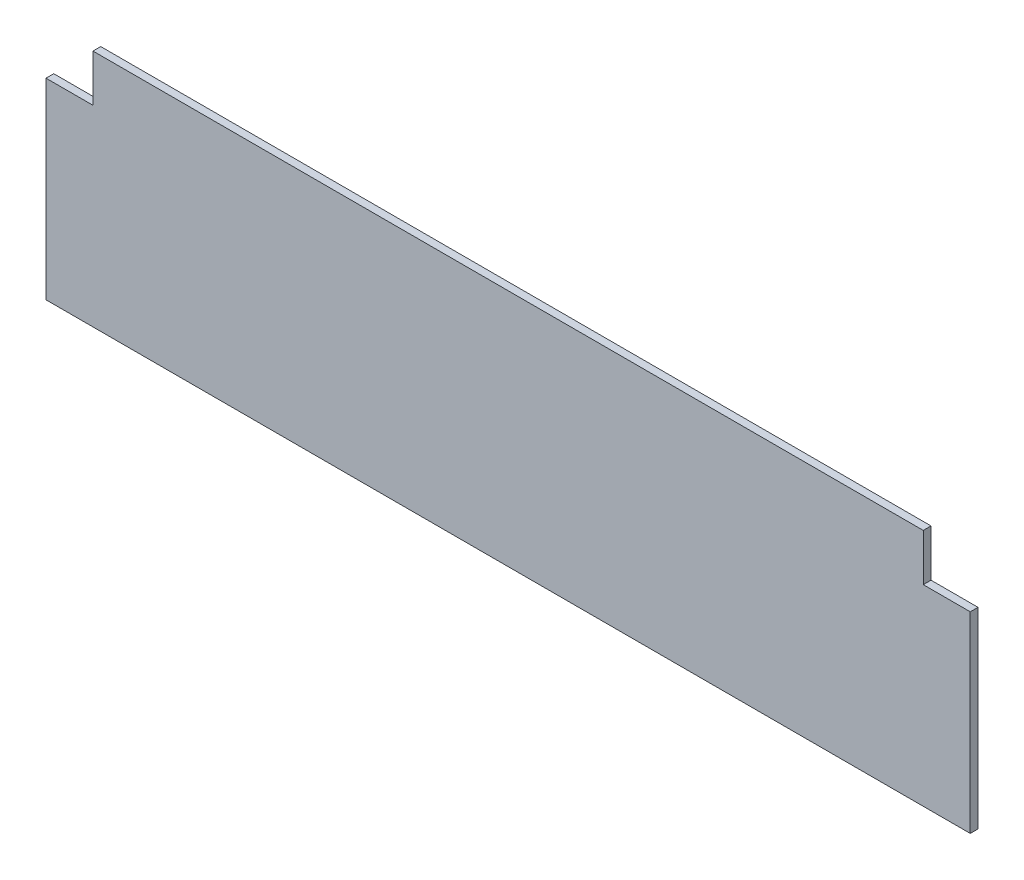
SolidWorks part; units mm, degrees
material "Balsa"
ref_plane "Front Plane" through (0, 0, 0) normal (0, 0, 1) x (1, 0, 0)
ref_plane "Top Plane" through (0, 0, 0) normal (0, 1, 0) x (1, 0, 0)
ref_plane "Right Plane" through (0, 0, 0) normal (1, 0, 0) x (0, 0, -1)
sketch "Sketch1" plane through (0, 0, 0) normal (0, 0, 1) x (1, 0, 0)
  line L0 (393.4, -121.5124) -> (393.4, -39.8043)
  line L1 (393.4, -39.8043) -> (0, -39.8043) construction
  line L2 (0, -39.8043) -> (0, -121.5124)
  line L3 (0, -121.5124) -> (393.4, -121.5124)
  line L4 (0, -138.3774) -> (0, -39.8043) construction
  line L5 (373.4, -39.8043) -> (20, -39.8043) construction
  line L6 (373.4, -39.8043) -> (373.4, -19.8043)
  line L7 (373.4, -19.8043) -> (20, -19.8043)
  line L8 (20, -39.8043) -> (20, -19.8043)
  line L9 (373.4, -39.8043) -> (20, -19.8043) construction
  line L10 (373.4, -19.8043) -> (20, -39.8043) construction
  line L13 (20.7, -19.8043) -> (372.7, -19.8043) construction
  line L14 (393.4, -39.8043) -> (393.4, -138.3812) construction
  line L19 (393.4, -39.8043) -> (373.4, -39.8043)
  line L20 (0, -39.8043) -> (20, -39.8043)
  point P2 (0, -121.5124)
  point P3 (393.4, -121.5124)
  point P12 (196.7, -29.8043)
  dimension "D1" = 20
  dimension "D2" = 20
  dimension "D3" = 20
extrude "Boss-Extrude1" add sketch "Sketch1" against normal blind 3.3 contours L2 L3 L0 L1 | L8 L1 L6 L7 region at (196.7, -71.4918, 0)
